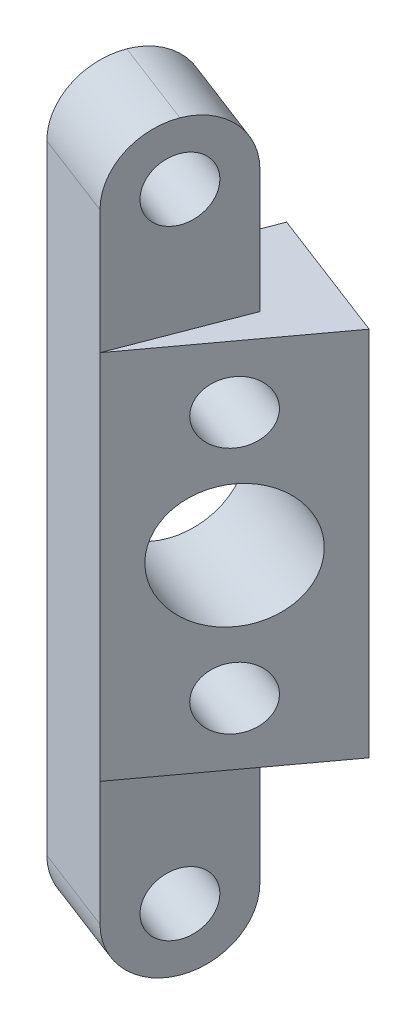
SolidWorks part; units mm, degrees
ref_plane "Front Plane" through (0, 0, 0) normal (0, 0, 1) x (1, 0, 0)
ref_plane "Top Plane" through (0, 0, 0) normal (0, 1, 0) x (1, 0, 0)
ref_plane "Right Plane" through (0, 0, 0) normal (1, 0, 0) x (0, 0, -1)
sketch "Sketch1" plane through (0, 0, 0) normal (0, 1, 0) x (1, 0, 0)
  line L0 (-9.4884, -9.302) -> (-0.9402, -8.0067)
  line L1 (-0.9402, -8.0067) -> (17.8614, 17.5105)
  line L2 (17.8614, 17.5105) -> (15.6059, 22.5764)
  line L3 (15.6059, 22.5764) -> (9.0677, 25.0862)
  line L4 (9.0677, 25.0862) -> (2.6079, 22.2101)
  line L5 (2.6079, 22.2101) -> (-9.4884, -9.302)
  line L6 (-0.9402, -8.0067) -> (2.6079, 22.2101) construction
  line L7 (17.8614, 17.5105) -> (-9.4884, -9.302) construction
  point P6 (0, 0)
  dimension "D1" = 33.754
  dimension "D2" = 31.5121
  dimension "D3" = 31.6958
  dimension "D4" = 5.5453
  dimension "D5" = 7.0034
  dimension "D6" = 7.0711
  dimension "D7" = 8.6458
  dimension "D8" = 135
extrude "Boss-Extrude1" add sketch "Sketch1" along normal mid plane 30
sketch "Sketch2" plane through (0, -15, 0) normal (0, -1, 0) x (1, 0, 0)
  line L6 (-8.7137, 8.6789) -> (3.0005, -21.8376)
  line L7 (3.0005, -21.8376) -> (9.0818, -24.5452)
  line L8 (9.0818, -24.5452) -> (15.2334, -22.1838)
  line L9 (15.2334, -22.1838) -> (17.2863, -17.5728)
  line L10 (17.2863, -17.5728) -> (-1.2198, 7.5433)
  line L11 (-1.2198, 7.5433) -> (-8.7137, 8.6789)
  line L12 (-9.4884, 9.302) -> (2.6079, -22.2101)
  line L13 (2.6079, -22.2101) -> (9.0677, -25.0862)
  line L14 (9.0677, -25.0862) -> (15.6059, -22.5764)
  line L15 (15.6059, -22.5764) -> (17.8614, -17.5105)
  line L16 (17.8614, -17.5105) -> (-0.9402, 8.0067)
  line L17 (-0.9402, 8.0067) -> (-9.4884, 9.302)
  line L18 (-9.4884, 9.302) -> (2.6079, -22.2101)
  line L19 (2.6079, -22.2101) -> (9.0677, -25.0862)
  line L20 (9.0677, -25.0862) -> (15.6059, -22.5764)
  line L21 (15.6059, -22.5764) -> (17.8614, -17.5105)
  line L22 (17.8614, -17.5105) -> (-0.9402, 8.0067)
  line L23 (-0.9402, 8.0067) -> (-9.4884, 9.302)
  dimension "D1" = 0
  dimension "D2" = 0.5
extrude "Cut-Extrude1" cut sketch "Sketch2" against normal through all
sketch "Sketch3" plane through (-4.6909, 0, -1.8007) normal (-0.9336, 0, -0.3584) x (-0.3584, 0, 0.9336)
  line L0 (11.2251, 0) -> (-3.2249, 0) construction
  line L1 (11.2251, 15) -> (11.2251, -15) construction
  circle A0 centre (-3.2249, 0) radius 5
  dimension "D1" = 10
  dimension "D2" = 14.45
extrude "Cut-Extrude2" cut sketch "Sketch3" against normal through all contours A0
sketch "Sketch5" plane through (-4.6909, 0, -1.8007) normal (-0.9336, 0, -0.3584) x (-0.3584, 0, 0.9336)
  line L0 (11.2251, 15) -> (-21.4624, 15) construction
  line L1 (-10.7249, -15) -> (4.2751, -15)
  line L2 (-10.7249, -15) -> (-10.7249, 15)
  line L3 (-10.7249, 15) -> (4.2751, 15)
  line L4 (4.2751, -15) -> (4.2751, 15)
  line L5 (-10.7249, -15) -> (4.2751, 15) construction
  line L6 (-10.7249, 15) -> (4.2751, -15) construction
  line L15 (-21.4624, -15) -> (11.2251, -15)
  line L16 (11.2251, -15) -> (11.2251, 15)
  line L17 (11.2251, 15) -> (-21.4624, 15)
  line L18 (-21.4624, 15) -> (-21.4624, -15)
  line L19 (-21.4624, -15) -> (11.2251, -15)
  line L20 (11.2251, -15) -> (11.2251, 15)
  line L21 (11.2251, 15) -> (-21.4624, 15)
  line L22 (-21.4624, 15) -> (-21.4624, -15)
  point P0 (-3.2249, 0)
  line M7 (-21.4624, -15) -> (11.2251, -15)
  line M8 (11.2251, -15) -> (11.2251, 15)
  line M9 (11.2251, 15) -> (-21.4624, 15)
  line M10 (-21.4624, 15) -> (-21.4624, -15)
  dimension "D1" = 15
  dimension "D2" = 0
extrude "Cut-Extrude3" cut sketch "Sketch5" against normal through all contours L2 M7 M9 M10 | L4 M7 M8 M9
sketch "Sketch7" plane through (-4.6909, 0, -1.8007) normal (-0.9336, 0, -0.3584) x (-0.3584, 0, 0.9336)
  line L0 (-3.2249, 15) -> (-3.2249, 10) construction
  line L2 (4.2751, 15) -> (-10.7249, 15) construction
  line L4 (-3.2249, 0) -> (9.0542, 0) construction
  circle A0 centre (-3.2249, 10) radius 2.5
  circle A1 centre (-3.2249, -10) radius 2.5
  dimension "D1" = 5
  dimension "D2" = 5
extrude "Cut-Extrude4" cut sketch "Sketch7" against normal through all
chamfer "Chamfer1" [suppressed] distance 1.5 angle 45
sketch "Sketch8" plane through (0, 15, 0) normal (0, 1, 0) x (1, 0, 0)
  line L0 (-2.6393, 7.1453) -> (-6.223, -2.1905)
  line L1 (-6.223, -2.1905) -> (0.7516, -4.8678)
  line L2 (0.7516, -4.8678) -> (4.3353, 4.468)
  line L3 (4.3353, 4.468) -> (-2.6393, 7.1453)
  dimension "D1" = 10
extrude "Boss-Extrude4" add sketch "Sketch8" along normal blind 15
sketch "Sketch9" plane through (2.2836, 0, 0.8766) normal (0.9336, 0, 0.3584) x (0.3584, 0, -0.9336)
  line L0 (0.7249, 30) -> (0.7249, 25) construction
  line L1 (-4.2751, 30) -> (5.7249, 30) construction
  circle A0 centre (0.7249, 25) radius 2.5
  dimension "D1" = 5
  dimension "D2" = 5
extrude "Cut-Extrude5" cut sketch "Sketch9" against normal blind 15
fillet "Fillet1" radius 5 2 edges at (-2.7357, 30, 3.5291) (0.848, 30, -5.8067)
mirror "Mirror1" about plane through (0, 0, 0) normal (0, 1, 0) of "Boss-Extrude4", "Cut-Extrude5", "Fillet1"
